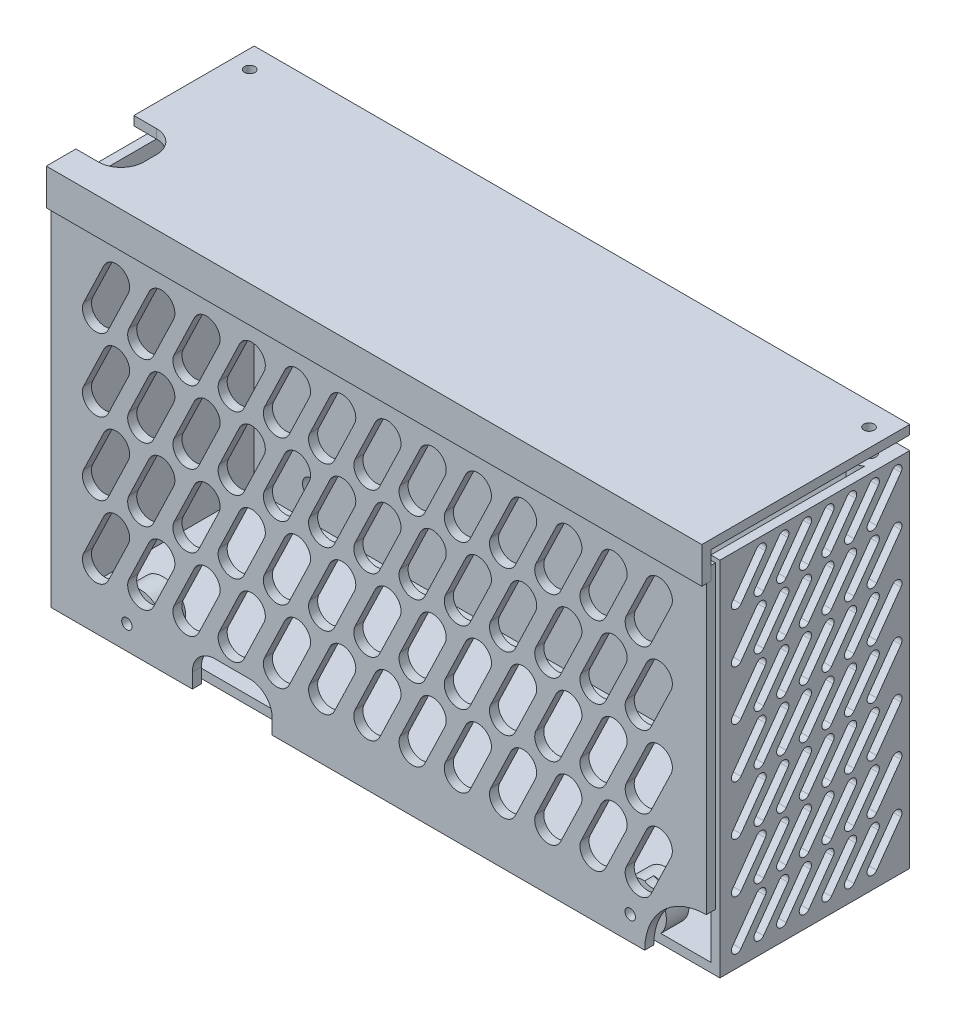
SolidWorks part; units mm, degrees
note: The reader was unsure of these and kept them because the rebuilt part matched: shared geometry of "Sketch1<3>".
ref_plane "Front Plane" through (0, 0, 0) normal (0, 0, 1) x (1, 0, 0)
ref_plane "Top Plane" through (0, 0, 0) normal (0, 1, 0) x (1, 0, 0)
ref_plane "Right Plane" through (0, 0, 0) normal (1, 0, 0) x (0, 0, -1)
sketch "Sketch1" plane through (0, 0, 0) normal (0, 1, 0) x (1, 0, 0)
  line L0 (-81.5, 0) -> (81.5, 0) construction
  line L1 (-58.6884, 41) -> (67.4713, 41) construction
  line L2 (67.4713, 41) -> (67.4713, -41) construction
  line L3 (67.4713, -41) -> (-58.6884, -41) construction
  line L4 (-58.6884, -41) -> (-58.6884, 41) construction
  line L6 (-72.4713, 52) -> (72.4713, 52)
  line L7 (-72.4713, 52) -> (-72.4713, -52)
  line L8 (-72.4713, -52) -> (72.4713, -52)
  line L9 (72.4713, 52) -> (72.4713, -52)
  line L10 (-72.4713, 52) -> (72.4713, -52) construction
  line L11 (-72.4713, -52) -> (72.4713, 52) construction
  circle A0 centre (0, -41) radius 2.5
  circle A1 centre (-58.6884, -41) radius 2.5
  circle A2 centre (67.4713, -41) radius 2.5
  circle A3 centre (67.4713, 41) radius 2.5
  circle A4 centre (0, 41) radius 2.5
  circle A5 centre (-58.6884, 41) radius 2.5
  point P15 (0, 0)
  point P16 (-58.6884, 0)
  dimension "D1" = 5
  dimension "D2" = 41
  dimension "D3" = 126.1597
  dimension "D4" = 11
  dimension "D5" = 5
  dimension "D6" = 58.6884
extrude "Boss-Extrude1" add sketch "Sketch1" along normal blind 80 contours L9 L6 L7 L8 A4 A0 A1 A2 A3 A5 | A5 | A4 | A3 | A2 | A0 | A1
sketch "Sketch3" plane through (0, 80, 0) normal (0, 1, 0) x (1, 0, 0)
  line L0 (0, -25) -> (0, -61.5668) construction
  line L1 (25, -25) -> (25, -61.5668)
  line L2 (-25, -25) -> (-25, -61.5668)
  line L3 (72.4713, 52) -> (72.4713, -52) construction
  line L4 (0, 0) -> (-25.24, 0)
  line L5 (0, 0) -> (0, -61.5668)
  line L8 (-72.4713, -52) -> (72.4713, -52)
  line L9 (-72.4713, -52) -> (-72.4713, 10.0228)
  line L10 (-72.4713, 10.0228) -> (72.4713, 10.0228)
  line L11 (72.4713, -52) -> (72.4713, 10.0228)
  arc A1 (25, -25) -> (-25, -25) centre (0, -25) ccw
  arc A2 (-25, -61.5668) -> (25, -61.5668) centre (0, -61.5668) ccw
  point P2 (0, -43.2834)
  dimension "D1" = 25
extrude "Cut-Extrude1" cut sketch "Sketch3" against normal through all
shell "Shell1" thickness 2 removed face at (0, 80, -31.0114) removed face at (0, 40, -10.0228)
extrude "Boss-Extrude3" add sketch "Sketch1<3>" against normal blind 2 contours A5 | A4 | A3
sketch "Sketch1<3>" plane through (0, 0, 0) normal (0, 1, 0) x (1, 0, 0) same geometry as "Sketch1"
move or copy body "Body-Move/Copy1" [suppressed] bodies to move or copy 112 copy no translate (0, 10.8787, 0) parameters "D1"=0, "D2"=10.8787, "D3"=0
sketch "Sketch12" plane through (-72.4713, 0, 0) normal (-1, 0, 0) x (0, 0, 1)
  line L1 (-37.3501, 10.3785) -> (-38.7935, 12.8785)
  line L2 (-38.7935, 12.8785) -> (-41.6803, 12.8785)
  line L3 (-41.6803, 12.8785) -> (-43.1237, 10.3785)
  line L4 (-43.1237, 10.3785) -> (-41.6803, 7.8785)
  line L5 (-41.6803, 7.8785) -> (-38.7935, 7.8785)
  line L6 (-38.7935, 7.8785) -> (-37.3501, 10.3785)
  circle A0 centre (-40.2369, 10.3785) radius 2.5 construction
  dimension "D1" = 5
sketch "Sketch13" plane through (0, 0, -50) normal (0, 0, 1) x (1, 0, 0)
  line L1 (-57.8, 8.6) -> (57.8, 8.6)
  line L2 (-57.8, 8.6) -> (-57.8, 73.4)
  line L3 (-57.8, 73.4) -> (57.8, 73.4)
  line L4 (57.8, 8.6) -> (57.8, 73.4)
  line L5 (-70.4713, 80) -> (70.4713, 80) construction
  line L6 (0, 73.4) -> (0, 80) construction
  line L7 (-57.8, 41) -> (-70.4713, 41) construction
  line L8 (-70.4713, 80) -> (-70.4713, 2) construction
  circle A0 centre (-57.8, 73.4) radius 2
  circle A1 centre (57.8, 73.4) radius 2
  circle A2 centre (57.8, 8.6) radius 2
  circle A3 centre (-57.8, 8.6) radius 2
  point P6 (0, 80)
  point P13 (-70.4713, 41)
  dimension "D3" = 4
  dimension "D1" = 115.6
  dimension "D2" = 64.8
ref_plane "Plane1" through (0, 83, 0) normal (0, 1, 0) x (1, 0, 0)
sketch "Sketch14" plane through (0, 83, 0) normal (0, 1, 0) x (1, 0, 0)
  line L0 (72.4713, 52) -> (72.4713, 10.0228) construction
  line L1 (-72.4713, 10.0228) -> (72.4713, 10.0228)
  line L2 (-72.4713, 10.0228) -> (-72.4713, 52)
  line L3 (-72.4713, 52) -> (72.4713, 52)
  line L4 (72.4713, 10.0228) -> (72.4713, 52)
  line L5 (-72.4713, 52) -> (72.4713, 52) construction
extrude "Boss-Extrude4" add sketch "Sketch14" along normal blind 2 separate body
ref_plane "Plane2" through (0, 0, -9.0228) normal (0, 0, 1) x (1, 0, 0)
sketch "Sketch15" plane through (0, 0, -9.0228) normal (0, 0, 1) x (1, 0, 0)
  line L1 (-72.4713, 0) -> (72.4713, 0)
  line L2 (-72.4713, 0) -> (-72.4713, 80)
  line L3 (-72.4713, 80) -> (72.4713, 80)
  line L4 (72.4713, 0) -> (72.4713, 80)
extrude "Boss-Extrude5" add sketch "Sketch15" along normal blind 2 separate body
sketch "Sketch16" plane through (0, 0, -10.0228) normal (0, 0, 1) x (1, 0, 0)
  line L10 (-70.4713, 5.2829) -> (-55.6426, 5.2829) construction
  line L11 (-70.4713, 2) -> (-70.4713, 80) construction
  line L12 (55.6426, 5.2829) -> (70.4713, 5.2829) construction
  line L13 (70.4713, 2) -> (70.4713, 80) construction
  line L14 (-55.6426, 2) -> (-55.6426, 5.2829) construction
  line L15 (55.6426, 5.2829) -> (55.6426, 2) construction
  line L16 (-70.4713, 2) -> (70.4713, 2) construction
  circle A0 centre (-55.6426, 5.2829) radius 2
  circle A1 centre (55.6426, 5.2829) radius 2
  circle A2 centre (-55.6426, 5.2829) radius 5
  circle A3 centre (55.6426, 5.2829) radius 5
  dimension "D1" = 4
  dimension "D2" = 3
extrude "Boss-Extrude6" add sketch "Sketch16" against normal blind 5 contours A3 | A2
sketch "Sketch17" plane through (0, 80, 0) normal (0, 1, 0) x (1, 0, 0)
  line L0 (-70.4713, 50) -> (70.4713, 50) construction
  line L1 (-60.6426, 10.0228) -> (-50.6426, 10.0228) construction
  line L2 (-70.4713, 50) -> (-70.4713, 10.0228) construction
  circle A0 centre (-68.4713, 47) radius 1.5
  circle A2 centre (-68.4713, 47) radius 3.6056
  point P0 (-55.6426, 50)
  point P5 (-55.6426, 10.0228)
  dimension "D1" = 3
  dimension "D2" = 3
  dimension "D4" = 2
extrude "Boss-Extrude7" add sketch "Sketch17" against normal blind 5
ref_plane "Plane3" through (0, 0, 0) normal (1, 0, 0) x (0, 0, -1)
mirror "Mirror1" about plane through (0, 0, 0) normal (1, 0, 0) of "Boss-Extrude7"
fillet "Fillet2" radius 10 2 edges at (68.4713, 75, -50) (-68.4713, 75, -50)
fillet "Fillet3" radius 2 2 edges at (-66.4713, 72.5, -50) (66.4713, 72.5, -50)
extrude "Cut-Extrude2" cut sketch "Sketch13" against normal blind 5 contours L3 A0 L2 | L2 A0 L3 | L2 A3 L1 | L1 A3 L2 | L4 A1 L3 | L3 A1 L4 | L1 A2 L4 | L4 A2 L1
sketch "Sketch19" plane through (0, 85, 0) normal (0, 1, 0) x (1, 0, 0)
  circle A0 centre (-68.4713, 47) radius 1.15
  circle A1 centre (68.4713, 47) radius 1.15
  dimension "D1" = 2.3
extrude "Cut-Extrude3" cut sketch "Sketch19" against normal blind 5
sketch "Sketch21" plane through (0, 0, -7.0228) normal (0, 0, 1) x (1, 0, 0)
  line L4 (-72.4713, 80) -> (-72.4713, 0)
  line L5 (-72.4713, 0) -> (72.4713, 0)
  line L6 (72.4713, 0) -> (72.4713, 80)
  line L7 (72.4713, 80) -> (-72.4713, 80)
  line L11 (72.4713, 80) -> (-72.4713, 80)
  dimension "D1" = 0
sketch "Sketch20" plane through (0, 0, -7.0228) normal (0, 0, 1) x (1, 0, 0)
  line L0 (72.4713, 0) -> (72.4713, 80) construction
  line L1 (-72.4713, 0) -> (72.4713, 0) construction
  line L2 (-72.4713, 80) -> (-72.4713, 0) construction
  line L3 (72.4713, 80) -> (-72.4713, 80) construction
  line L4 (72.4713, 0) -> (72.4713, 80)
  line L5 (-72.4713, 0) -> (72.4713, 0)
  line L6 (-72.4713, 80) -> (-72.4713, 0)
  line L7 (72.4713, 80) -> (-72.4713, 80)
  line L8 (-62.4713, 10) -> (62.4713, 10)
  line L9 (62.4713, 10) -> (62.4713, 70)
  line L10 (62.4713, 70) -> (-62.4713, 70)
  line L11 (-62.4713, 70) -> (-62.4713, 10)
  line L12 (-62.4713, 60.7598) -> (-58.034, 70) construction
  line L13 (-65.1756, 62.0585) -> (-60.7383, 71.2987)
  line L14 (-59.767, 59.4612) -> (-55.3297, 68.7013)
  line L15 (-62.4713, 70) -> (62.4713, 10) construction
  arc A0 (-65.1756, 62.0585) -> (-59.767, 59.4612) centre (-62.4713, 60.7598) ccw
  arc A1 (-55.3297, 68.7013) -> (-60.7383, 71.2987) centre (-58.034, 70) ccw
  point P10 (-60.2527, 65.3799)
  dimension "D2" = 3
  dimension "D3" = 4
  dimension "D4" = 10.2504
extrude "Cut-Extrude4" cut sketch "Sketch20" against normal blind 5 contours L10 A1 L13 | L14 A1 L10 L13 L11 A0 | L13 A0 L11
sketch "Sketch23" plane through (0, 0, -7.0228) normal (0, 0, 1) x (1, 0, 0)
  line L0 (-62.4713, 70) -> (62.4713, 10)
pattern_linear "LPattern7" [suppressed] count 9 spacing 10 along (0.9014, -0.4329, 0)
pattern_linear "LPattern8" count 13 spacing 10 along (1, 0, 0) count 4 spacing 16 along (0, -1, 0) of "Cut-Extrude4"
sketch "Sketch24" plane through (0, 0, -7.0228) normal (0, 0, 1) x (1, 0, 0)
  circle A0 centre (-55.6426, 5.2829) radius 1.15
  circle A1 centre (55.6426, 5.2829) radius 1.15
  dimension "D1" = 2.3
extrude "Cut-Extrude5" cut sketch "Sketch24" against normal through all
sketch "Sketch25" plane through (0, 0, -7.0228) normal (0, 0, 1) x (1, 0, 0)
  circle A0 centre (72.4713, 0) radius 13.6291
extrude "Cut-Extrude6" cut sketch "Sketch25" against normal through all
sketch "Sketch26" plane through (72.4713, 0, 0) normal (1, 0, 0) x (0, 0, -1)
  line L0 (13.7314, 69.9645) -> (19.1095, 77.5009) construction
  line L1 (12.7812, 70.6426) -> (18.1592, 78.179)
  line L2 (14.6817, 69.2864) -> (20.0597, 76.8228)
  line L3 (18.7314, 69.9645) -> (24.1095, 77.5009) construction
  line L4 (17.7812, 70.6426) -> (23.1592, 78.179)
  line L5 (19.6817, 69.2864) -> (25.0597, 76.8228)
  line L6 (23.7314, 69.9645) -> (29.1095, 77.5009) construction
  line L7 (22.7812, 70.6426) -> (28.1592, 78.179)
  line L8 (24.6817, 69.2864) -> (30.0597, 76.8228)
  line L9 (28.7314, 69.9645) -> (34.1095, 77.5009) construction
  line L10 (27.7812, 70.6426) -> (33.1592, 78.179)
  line L11 (29.6817, 69.2864) -> (35.0597, 76.8228)
  line L12 (33.7314, 69.9645) -> (39.1095, 77.5009) construction
  line L13 (32.7812, 70.6426) -> (38.1592, 78.179)
  line L14 (34.6817, 69.2864) -> (40.0597, 76.8228)
  line L15 (38.7314, 69.9645) -> (44.1095, 77.5009) construction
  line L16 (37.7812, 70.6426) -> (43.1592, 78.179)
  line L17 (39.6817, 69.2864) -> (45.0597, 76.8228)
  line L18 (43.7314, 69.9645) -> (49.1095, 77.5009) construction
  line L19 (42.7812, 70.6426) -> (48.1592, 78.179)
  line L20 (44.6817, 69.2864) -> (50.0597, 76.8228)
  line L21 (18.7314, 58.9645) -> (24.1095, 66.5009) construction
  line L22 (17.7812, 59.6426) -> (23.1592, 67.179)
  line L23 (19.6817, 58.2864) -> (25.0597, 65.8228)
  line L24 (23.7314, 58.9645) -> (29.1095, 66.5009) construction
  line L25 (22.7812, 59.6426) -> (28.1592, 67.179)
  line L26 (24.6817, 58.2864) -> (30.0597, 65.8228)
  line L27 (28.7314, 58.9645) -> (34.1095, 66.5009) construction
  line L28 (27.7812, 59.6426) -> (33.1592, 67.179)
  line L29 (29.6817, 58.2864) -> (35.0597, 65.8228)
  line L30 (33.7314, 58.9645) -> (39.1095, 66.5009) construction
  line L31 (32.7812, 59.6426) -> (38.1592, 67.179)
  line L32 (34.6817, 58.2864) -> (40.0597, 65.8228)
  line L33 (38.7314, 58.9645) -> (44.1095, 66.5009) construction
  line L34 (37.7812, 59.6426) -> (43.1592, 67.179)
  line L35 (39.6817, 58.2864) -> (45.0597, 65.8228)
  line L36 (43.7314, 58.9645) -> (49.1095, 66.5009) construction
  line L37 (42.7812, 59.6426) -> (48.1592, 67.179)
  line L38 (44.6817, 58.2864) -> (50.0597, 65.8228)
  line L39 (18.7314, 47.9645) -> (24.1095, 55.5009) construction
  line L40 (17.7812, 48.6426) -> (23.1592, 56.179)
  line L41 (19.6817, 47.2864) -> (25.0597, 54.8228)
  line L42 (23.7314, 47.9645) -> (29.1095, 55.5009) construction
  line L43 (22.7812, 48.6426) -> (28.1592, 56.179)
  line L44 (24.6817, 47.2864) -> (30.0597, 54.8228)
  line L45 (28.7314, 47.9645) -> (34.1095, 55.5009) construction
  line L46 (27.7812, 48.6426) -> (33.1592, 56.179)
  line L47 (29.6817, 47.2864) -> (35.0597, 54.8228)
  line L48 (33.7314, 47.9645) -> (39.1095, 55.5009) construction
  line L49 (32.7812, 48.6426) -> (38.1592, 56.179)
  line L50 (34.6817, 47.2864) -> (40.0597, 54.8228)
  line L51 (38.7314, 47.9645) -> (44.1095, 55.5009) construction
  line L52 (37.7812, 48.6426) -> (43.1592, 56.179)
  line L53 (39.6817, 47.2864) -> (45.0597, 54.8228)
  line L54 (43.7314, 47.9645) -> (49.1095, 55.5009) construction
  line L55 (42.7812, 48.6426) -> (48.1592, 56.179)
  line L56 (44.6817, 47.2864) -> (50.0597, 54.8228)
  line L57 (18.7314, 36.9645) -> (24.1095, 44.5009) construction
  line L58 (17.7812, 37.6426) -> (23.1592, 45.179)
  line L59 (19.6817, 36.2864) -> (25.0597, 43.8228)
  line L60 (23.7314, 36.9645) -> (29.1095, 44.5009) construction
  line L61 (22.7812, 37.6426) -> (28.1592, 45.179)
  line L62 (24.6817, 36.2864) -> (30.0597, 43.8228)
  line L63 (28.7314, 36.9645) -> (34.1095, 44.5009) construction
  line L64 (27.7812, 37.6426) -> (33.1592, 45.179)
  line L65 (29.6817, 36.2864) -> (35.0597, 43.8228)
  line L66 (33.7314, 36.9645) -> (39.1095, 44.5009) construction
  line L67 (32.7812, 37.6426) -> (38.1592, 45.179)
  line L68 (34.6817, 36.2864) -> (40.0597, 43.8228)
  line L69 (38.7314, 36.9645) -> (44.1095, 44.5009) construction
  line L70 (37.7812, 37.6426) -> (43.1592, 45.179)
  line L71 (39.6817, 36.2864) -> (45.0597, 43.8228)
  line L72 (43.7314, 36.9645) -> (49.1095, 44.5009) construction
  line L73 (42.7812, 37.6426) -> (48.1592, 45.179)
  line L74 (44.6817, 36.2864) -> (50.0597, 43.8228)
  line L75 (18.7314, 25.9645) -> (24.1095, 33.5009) construction
  line L76 (17.7812, 26.6426) -> (23.1592, 34.179)
  line L77 (19.6817, 25.2864) -> (25.0597, 32.8228)
  line L78 (23.7314, 25.9645) -> (29.1095, 33.5009) construction
  line L79 (22.7812, 26.6426) -> (28.1592, 34.179)
  line L80 (24.6817, 25.2864) -> (30.0597, 32.8228)
  line L81 (28.7314, 25.9645) -> (34.1095, 33.5009) construction
  line L82 (27.7812, 26.6426) -> (33.1592, 34.179)
  line L83 (29.6817, 25.2864) -> (35.0597, 32.8228)
  line L84 (33.7314, 25.9645) -> (39.1095, 33.5009) construction
  line L85 (32.7812, 26.6426) -> (38.1592, 34.179)
  line L86 (34.6817, 25.2864) -> (40.0597, 32.8228)
  line L87 (38.7314, 25.9645) -> (44.1095, 33.5009) construction
  line L88 (37.7812, 26.6426) -> (43.1592, 34.179)
  line L89 (39.6817, 25.2864) -> (45.0597, 32.8228)
  line L90 (43.7314, 25.9645) -> (49.1095, 33.5009) construction
  line L91 (42.7812, 26.6426) -> (48.1592, 34.179)
  line L92 (44.6817, 25.2864) -> (50.0597, 32.8228)
  line L93 (18.7314, 14.9645) -> (24.1095, 22.5009) construction
  line L94 (17.7812, 15.6426) -> (23.1592, 23.179)
  line L95 (19.6817, 14.2864) -> (25.0597, 21.8228)
  line L96 (23.7314, 14.9645) -> (29.1095, 22.5009) construction
  line L97 (22.7812, 15.6426) -> (28.1592, 23.179)
  line L98 (24.6817, 14.2864) -> (30.0597, 21.8228)
  line L99 (28.7314, 14.9645) -> (34.1095, 22.5009) construction
  line L100 (27.7812, 15.6426) -> (33.1592, 23.179)
  line L101 (29.6817, 14.2864) -> (35.0597, 21.8228)
  line L102 (33.7314, 14.9645) -> (39.1095, 22.5009) construction
  line L103 (32.7812, 15.6426) -> (38.1592, 23.179)
  line L104 (34.6817, 14.2864) -> (40.0597, 21.8228)
  line L105 (38.7314, 14.9645) -> (44.1095, 22.5009) construction
  line L106 (37.7812, 15.6426) -> (43.1592, 23.179)
  line L107 (39.6817, 14.2864) -> (45.0597, 21.8228)
  line L108 (43.7314, 14.9645) -> (49.1095, 22.5009) construction
  line L109 (42.7812, 15.6426) -> (48.1592, 23.179)
  line L110 (44.6817, 14.2864) -> (50.0597, 21.8228)
  line L111 (18.7314, 3.9645) -> (24.1095, 11.5009) construction
  line L112 (17.7812, 4.6426) -> (23.1592, 12.179)
  line L113 (19.6817, 3.2864) -> (25.0597, 10.8228)
  line L114 (23.7314, 3.9645) -> (29.1095, 11.5009) construction
  line L115 (22.7812, 4.6426) -> (28.1592, 12.179)
  line L116 (24.6817, 3.2864) -> (30.0597, 10.8228)
  line L117 (28.7314, 3.9645) -> (34.1095, 11.5009) construction
  line L118 (27.7812, 4.6426) -> (33.1592, 12.179)
  line L119 (29.6817, 3.2864) -> (35.0597, 10.8228)
  line L120 (33.7314, 3.9645) -> (39.1095, 11.5009) construction
  line L121 (32.7812, 4.6426) -> (38.1592, 12.179)
  line L122 (34.6817, 3.2864) -> (40.0597, 10.8228)
  line L123 (38.7314, 3.9645) -> (44.1095, 11.5009) construction
  line L124 (37.7812, 4.6426) -> (43.1592, 12.179)
  line L125 (39.6817, 3.2864) -> (45.0597, 10.8228)
  line L126 (43.7314, 3.9645) -> (49.1095, 11.5009) construction
  line L127 (42.7812, 4.6426) -> (48.1592, 12.179)
  line L128 (44.6817, 3.2864) -> (50.0597, 10.8228)
  line L129 (13.7314, 58.9645) -> (19.1095, 66.5009) construction
  line L130 (12.7812, 59.6426) -> (18.1592, 67.179)
  line L131 (14.6817, 58.2864) -> (20.0597, 65.8228)
  line L132 (13.7314, 47.9645) -> (19.1095, 55.5009) construction
  line L133 (12.7812, 48.6426) -> (18.1592, 56.179)
  line L134 (14.6817, 47.2864) -> (20.0597, 54.8228)
  line L135 (13.7314, 36.9645) -> (19.1095, 44.5009) construction
  line L136 (12.7812, 37.6426) -> (18.1592, 45.179)
  line L137 (14.6817, 36.2864) -> (20.0597, 43.8228)
  line L138 (13.7314, 25.9645) -> (19.1095, 33.5009) construction
  line L139 (12.7812, 26.6426) -> (18.1592, 34.179)
  line L140 (14.6817, 25.2864) -> (20.0597, 32.8228)
  line L141 (13.7314, 14.9645) -> (19.1095, 22.5009) construction
  line L142 (12.7812, 15.6426) -> (18.1592, 23.179)
  line L143 (14.6817, 14.2864) -> (20.0597, 21.8228)
  line L144 (13.7314, 3.9645) -> (19.1095, 11.5009) construction
  line L145 (12.7812, 4.6426) -> (18.1592, 12.179)
  line L146 (14.6817, 3.2864) -> (20.0597, 10.8228)
  arc A0 (12.7812, 70.6426) -> (14.6817, 69.2864) centre (13.7314, 69.9645) ccw
  arc A1 (20.0597, 76.8228) -> (18.1592, 78.179) centre (19.1095, 77.5009) ccw
  arc A2 (17.7812, 70.6426) -> (19.6817, 69.2864) centre (18.7314, 69.9645) ccw
  arc A3 (25.0597, 76.8228) -> (23.1592, 78.179) centre (24.1095, 77.5009) ccw
  arc A4 (22.7812, 70.6426) -> (24.6817, 69.2864) centre (23.7314, 69.9645) ccw
  arc A5 (30.0597, 76.8228) -> (28.1592, 78.179) centre (29.1095, 77.5009) ccw
  arc A6 (27.7812, 70.6426) -> (29.6817, 69.2864) centre (28.7314, 69.9645) ccw
  arc A7 (35.0597, 76.8228) -> (33.1592, 78.179) centre (34.1095, 77.5009) ccw
  arc A8 (32.7812, 70.6426) -> (34.6817, 69.2864) centre (33.7314, 69.9645) ccw
  arc A9 (40.0597, 76.8228) -> (38.1592, 78.179) centre (39.1095, 77.5009) ccw
  arc A10 (37.7812, 70.6426) -> (39.6817, 69.2864) centre (38.7314, 69.9645) ccw
  arc A11 (45.0597, 76.8228) -> (43.1592, 78.179) centre (44.1095, 77.5009) ccw
  arc A12 (42.7812, 70.6426) -> (44.6817, 69.2864) centre (43.7314, 69.9645) ccw
  arc A13 (50.0597, 76.8228) -> (48.1592, 78.179) centre (49.1095, 77.5009) ccw
  arc A14 (17.7812, 59.6426) -> (19.6817, 58.2864) centre (18.7314, 58.9645) ccw
  arc A15 (25.0597, 65.8228) -> (23.1592, 67.179) centre (24.1095, 66.5009) ccw
  arc A16 (22.7812, 59.6426) -> (24.6817, 58.2864) centre (23.7314, 58.9645) ccw
  arc A17 (30.0597, 65.8228) -> (28.1592, 67.179) centre (29.1095, 66.5009) ccw
  arc A18 (27.7812, 59.6426) -> (29.6817, 58.2864) centre (28.7314, 58.9645) ccw
  arc A19 (35.0597, 65.8228) -> (33.1592, 67.179) centre (34.1095, 66.5009) ccw
  arc A20 (32.7812, 59.6426) -> (34.6817, 58.2864) centre (33.7314, 58.9645) ccw
  arc A21 (40.0597, 65.8228) -> (38.1592, 67.179) centre (39.1095, 66.5009) ccw
  arc A22 (37.7812, 59.6426) -> (39.6817, 58.2864) centre (38.7314, 58.9645) ccw
  arc A23 (45.0597, 65.8228) -> (43.1592, 67.179) centre (44.1095, 66.5009) ccw
  arc A24 (42.7812, 59.6426) -> (44.6817, 58.2864) centre (43.7314, 58.9645) ccw
  arc A25 (50.0597, 65.8228) -> (48.1592, 67.179) centre (49.1095, 66.5009) ccw
  arc A26 (17.7812, 48.6426) -> (19.6817, 47.2864) centre (18.7314, 47.9645) ccw
  arc A27 (25.0597, 54.8228) -> (23.1592, 56.179) centre (24.1095, 55.5009) ccw
  arc A28 (22.7812, 48.6426) -> (24.6817, 47.2864) centre (23.7314, 47.9645) ccw
  arc A29 (30.0597, 54.8228) -> (28.1592, 56.179) centre (29.1095, 55.5009) ccw
  arc A30 (27.7812, 48.6426) -> (29.6817, 47.2864) centre (28.7314, 47.9645) ccw
  arc A31 (35.0597, 54.8228) -> (33.1592, 56.179) centre (34.1095, 55.5009) ccw
  arc A32 (32.7812, 48.6426) -> (34.6817, 47.2864) centre (33.7314, 47.9645) ccw
  arc A33 (40.0597, 54.8228) -> (38.1592, 56.179) centre (39.1095, 55.5009) ccw
  arc A34 (37.7812, 48.6426) -> (39.6817, 47.2864) centre (38.7314, 47.9645) ccw
  arc A35 (45.0597, 54.8228) -> (43.1592, 56.179) centre (44.1095, 55.5009) ccw
  arc A36 (42.7812, 48.6426) -> (44.6817, 47.2864) centre (43.7314, 47.9645) ccw
  arc A37 (50.0597, 54.8228) -> (48.1592, 56.179) centre (49.1095, 55.5009) ccw
  arc A38 (17.7812, 37.6426) -> (19.6817, 36.2864) centre (18.7314, 36.9645) ccw
  arc A39 (25.0597, 43.8228) -> (23.1592, 45.179) centre (24.1095, 44.5009) ccw
  arc A40 (22.7812, 37.6426) -> (24.6817, 36.2864) centre (23.7314, 36.9645) ccw
  arc A41 (30.0597, 43.8228) -> (28.1592, 45.179) centre (29.1095, 44.5009) ccw
  arc A42 (27.7812, 37.6426) -> (29.6817, 36.2864) centre (28.7314, 36.9645) ccw
  arc A43 (35.0597, 43.8228) -> (33.1592, 45.179) centre (34.1095, 44.5009) ccw
  arc A44 (32.7812, 37.6426) -> (34.6817, 36.2864) centre (33.7314, 36.9645) ccw
  arc A45 (40.0597, 43.8228) -> (38.1592, 45.179) centre (39.1095, 44.5009) ccw
  arc A46 (37.7812, 37.6426) -> (39.6817, 36.2864) centre (38.7314, 36.9645) ccw
  arc A47 (45.0597, 43.8228) -> (43.1592, 45.179) centre (44.1095, 44.5009) ccw
  arc A48 (42.7812, 37.6426) -> (44.6817, 36.2864) centre (43.7314, 36.9645) ccw
  arc A49 (50.0597, 43.8228) -> (48.1592, 45.179) centre (49.1095, 44.5009) ccw
  arc A50 (17.7812, 26.6426) -> (19.6817, 25.2864) centre (18.7314, 25.9645) ccw
  arc A51 (25.0597, 32.8228) -> (23.1592, 34.179) centre (24.1095, 33.5009) ccw
  arc A52 (22.7812, 26.6426) -> (24.6817, 25.2864) centre (23.7314, 25.9645) ccw
  arc A53 (30.0597, 32.8228) -> (28.1592, 34.179) centre (29.1095, 33.5009) ccw
  arc A54 (27.7812, 26.6426) -> (29.6817, 25.2864) centre (28.7314, 25.9645) ccw
  arc A55 (35.0597, 32.8228) -> (33.1592, 34.179) centre (34.1095, 33.5009) ccw
  arc A56 (32.7812, 26.6426) -> (34.6817, 25.2864) centre (33.7314, 25.9645) ccw
  arc A57 (40.0597, 32.8228) -> (38.1592, 34.179) centre (39.1095, 33.5009) ccw
  arc A58 (37.7812, 26.6426) -> (39.6817, 25.2864) centre (38.7314, 25.9645) ccw
  arc A59 (45.0597, 32.8228) -> (43.1592, 34.179) centre (44.1095, 33.5009) ccw
  arc A60 (42.7812, 26.6426) -> (44.6817, 25.2864) centre (43.7314, 25.9645) ccw
  arc A61 (50.0597, 32.8228) -> (48.1592, 34.179) centre (49.1095, 33.5009) ccw
  arc A62 (17.7812, 15.6426) -> (19.6817, 14.2864) centre (18.7314, 14.9645) ccw
  arc A63 (25.0597, 21.8228) -> (23.1592, 23.179) centre (24.1095, 22.5009) ccw
  arc A64 (22.7812, 15.6426) -> (24.6817, 14.2864) centre (23.7314, 14.9645) ccw
  arc A65 (30.0597, 21.8228) -> (28.1592, 23.179) centre (29.1095, 22.5009) ccw
  arc A66 (27.7812, 15.6426) -> (29.6817, 14.2864) centre (28.7314, 14.9645) ccw
  arc A67 (35.0597, 21.8228) -> (33.1592, 23.179) centre (34.1095, 22.5009) ccw
  arc A68 (32.7812, 15.6426) -> (34.6817, 14.2864) centre (33.7314, 14.9645) ccw
  arc A69 (40.0597, 21.8228) -> (38.1592, 23.179) centre (39.1095, 22.5009) ccw
  arc A70 (37.7812, 15.6426) -> (39.6817, 14.2864) centre (38.7314, 14.9645) ccw
  arc A71 (45.0597, 21.8228) -> (43.1592, 23.179) centre (44.1095, 22.5009) ccw
  arc A72 (42.7812, 15.6426) -> (44.6817, 14.2864) centre (43.7314, 14.9645) ccw
  arc A73 (50.0597, 21.8228) -> (48.1592, 23.179) centre (49.1095, 22.5009) ccw
  arc A74 (17.7812, 4.6426) -> (19.6817, 3.2864) centre (18.7314, 3.9645) ccw
  arc A75 (25.0597, 10.8228) -> (23.1592, 12.179) centre (24.1095, 11.5009) ccw
  arc A76 (22.7812, 4.6426) -> (24.6817, 3.2864) centre (23.7314, 3.9645) ccw
  arc A77 (30.0597, 10.8228) -> (28.1592, 12.179) centre (29.1095, 11.5009) ccw
  arc A78 (27.7812, 4.6426) -> (29.6817, 3.2864) centre (28.7314, 3.9645) ccw
  arc A79 (35.0597, 10.8228) -> (33.1592, 12.179) centre (34.1095, 11.5009) ccw
  arc A80 (32.7812, 4.6426) -> (34.6817, 3.2864) centre (33.7314, 3.9645) ccw
  arc A81 (40.0597, 10.8228) -> (38.1592, 12.179) centre (39.1095, 11.5009) ccw
  arc A82 (37.7812, 4.6426) -> (39.6817, 3.2864) centre (38.7314, 3.9645) ccw
  arc A83 (45.0597, 10.8228) -> (43.1592, 12.179) centre (44.1095, 11.5009) ccw
  arc A84 (42.7812, 4.6426) -> (44.6817, 3.2864) centre (43.7314, 3.9645) ccw
  arc A85 (50.0597, 10.8228) -> (48.1592, 12.179) centre (49.1095, 11.5009) ccw
  arc A86 (12.7812, 59.6426) -> (14.6817, 58.2864) centre (13.7314, 58.9645) ccw
  arc A87 (20.0597, 65.8228) -> (18.1592, 67.179) centre (19.1095, 66.5009) ccw
  arc A88 (12.7812, 48.6426) -> (14.6817, 47.2864) centre (13.7314, 47.9645) ccw
  arc A89 (20.0597, 54.8228) -> (18.1592, 56.179) centre (19.1095, 55.5009) ccw
  arc A90 (12.7812, 37.6426) -> (14.6817, 36.2864) centre (13.7314, 36.9645) ccw
  arc A91 (20.0597, 43.8228) -> (18.1592, 45.179) centre (19.1095, 44.5009) ccw
  arc A92 (12.7812, 26.6426) -> (14.6817, 25.2864) centre (13.7314, 25.9645) ccw
  arc A93 (20.0597, 32.8228) -> (18.1592, 34.179) centre (19.1095, 33.5009) ccw
  arc A94 (12.7812, 15.6426) -> (14.6817, 14.2864) centre (13.7314, 14.9645) ccw
  arc A95 (20.0597, 21.8228) -> (18.1592, 23.179) centre (19.1095, 22.5009) ccw
  arc A96 (12.7812, 4.6426) -> (14.6817, 3.2864) centre (13.7314, 3.9645) ccw
  arc A97 (20.0597, 10.8228) -> (18.1592, 12.179) centre (19.1095, 11.5009) ccw
  point P2 (16.4205, 73.7327)
  point P12 (21.4205, 73.7327)
  point P19 (26.4205, 73.7327)
  point P26 (31.4205, 73.7327)
  point P33 (36.4205, 73.7327)
  point P40 (41.4205, 73.7327)
  point P47 (46.4205, 73.7327)
  point P54 (21.4205, 62.7327)
  point P61 (26.4205, 62.7327)
  point P68 (31.4205, 62.7327)
  point P75 (36.4205, 62.7327)
  point P82 (41.4205, 62.7327)
  point P89 (46.4205, 62.7327)
  point P96 (21.4205, 51.7327)
  point P103 (26.4205, 51.7327)
  point P110 (31.4205, 51.7327)
  point P117 (36.4205, 51.7327)
  point P124 (41.4205, 51.7327)
  point P131 (46.4205, 51.7327)
  point P138 (21.4205, 40.7327)
  point P145 (26.4205, 40.7327)
  point P152 (31.4205, 40.7327)
  point P159 (36.4205, 40.7327)
  point P166 (41.4205, 40.7327)
  point P173 (46.4205, 40.7327)
  point P180 (21.4205, 29.7327)
  point P187 (26.4205, 29.7327)
  point P194 (31.4205, 29.7327)
  point P201 (36.4205, 29.7327)
  point P208 (41.4205, 29.7327)
  point P215 (46.4205, 29.7327)
  point P222 (21.4205, 18.7327)
  point P229 (26.4205, 18.7327)
  point P236 (31.4205, 18.7327)
  point P243 (36.4205, 18.7327)
  point P250 (41.4205, 18.7327)
  point P257 (46.4205, 18.7327)
  point P264 (21.4205, 7.7327)
  point P271 (26.4205, 7.7327)
  point P278 (31.4205, 7.7327)
  point P285 (36.4205, 7.7327)
  point P292 (41.4205, 7.7327)
  point P299 (46.4205, 7.7327)
  point P306 (16.4205, 62.7327)
  point P313 (16.4205, 51.7327)
  point P320 (16.4205, 40.7327)
  point P327 (16.4205, 29.7327)
  point P334 (16.4205, 18.7327)
  point P341 (16.4205, 7.7327)
  dimension "D1" = 7
  dimension "D2" = 7
extrude "Cut-Extrude7" cut sketch "Sketch26" against normal up to surface (2 mm away) up to face at (70.4713, 50.6766, -34.902)
sketch "Sketch27" plane through (0, 0, -10.0228) normal (0, 0, 1) x (1, 0, 0)
  line L4 (-72.4713, 83) -> (72.4713, 83)
  line L5 (72.4713, 83) -> (72.4713, 85)
  line L6 (72.4713, 85) -> (-72.4713, 85)
  line L7 (-72.4713, 85) -> (-72.4713, 83)
  line L8 (-72.4713, 83) -> (72.4713, 83)
  line L9 (72.4713, 83) -> (72.4713, 85)
  line L10 (72.4713, 85) -> (-72.4713, 85)
  line L11 (-72.4713, 85) -> (-72.4713, 83)
  dimension "D1" = 0
extrude "Boss-Extrude8" add sketch "Sketch27" along normal blind 2
sketch "Sketch28" plane through (72.4713, 0, 0) normal (1, 0, 0) x (0, 0, -1)
  line L1 (8.0228, 85) -> (6.0228, 85)
  line L2 (8.0228, 85) -> (8.0228, 77)
  line L3 (8.0228, 77) -> (6.0228, 77)
  line L4 (6.0228, 85) -> (6.0228, 77)
  dimension "D1" = 8
  dimension "D2" = 2
extrude "Boss-Extrude9" add sketch "Sketch28" against normal up to surface (144.9426 mm away) up to face at (-72.4713, 84, -30.0114)
sketch "Sketch29" plane through (0, 85, 0) normal (0, 1, 0) x (1, 0, 0)
  line L0 (-72.4713, 52) -> (-72.4713, 6.0228) construction
  line L1 (-72.4713, 25.3919) -> (-62.4713, 25.3919)
  line L2 (-72.4713, 25.3919) -> (-72.4713, 12.5712)
  line L3 (-72.4713, 12.5712) -> (-62.4713, 12.5712)
  line L4 (-62.4713, 25.3919) -> (-62.4713, 12.5712)
  dimension "D1" = 10
extrude "Cut-Extrude8" cut sketch "Sketch29" against normal up to surface (2 mm away) up to face at (-68.4713, 83, -48.15)
fillet "Fillet4" radius 5 2 edges at (-62.4713, 84, -12.5712) (-62.4713, 84, -25.3919)
sketch "Sketch30" plane through (0, 0, -7.0228) normal (0, 0, 1) x (1, 0, 0)
  line L0 (-72.4713, 0) -> (58.8422, 0) construction
  line L1 (-41.1688, 0) -> (-23.5038, 0)
  line L2 (-41.1688, 0) -> (-41.1688, 8.2909)
  line L3 (-41.1688, 8.2909) -> (-23.5038, 8.2909)
  line L4 (-23.5038, 0) -> (-23.5038, 8.2909)
extrude "Cut-Extrude9" cut sketch "Sketch30" against normal up to surface (2 mm away) up to face at (11.2039, 35.2904, -9.0228)
fillet "Fillet5" radius 5 2 edges at (-41.1688, 8.2909, -8.0228) (-23.5038, 8.2909, -8.0228)
